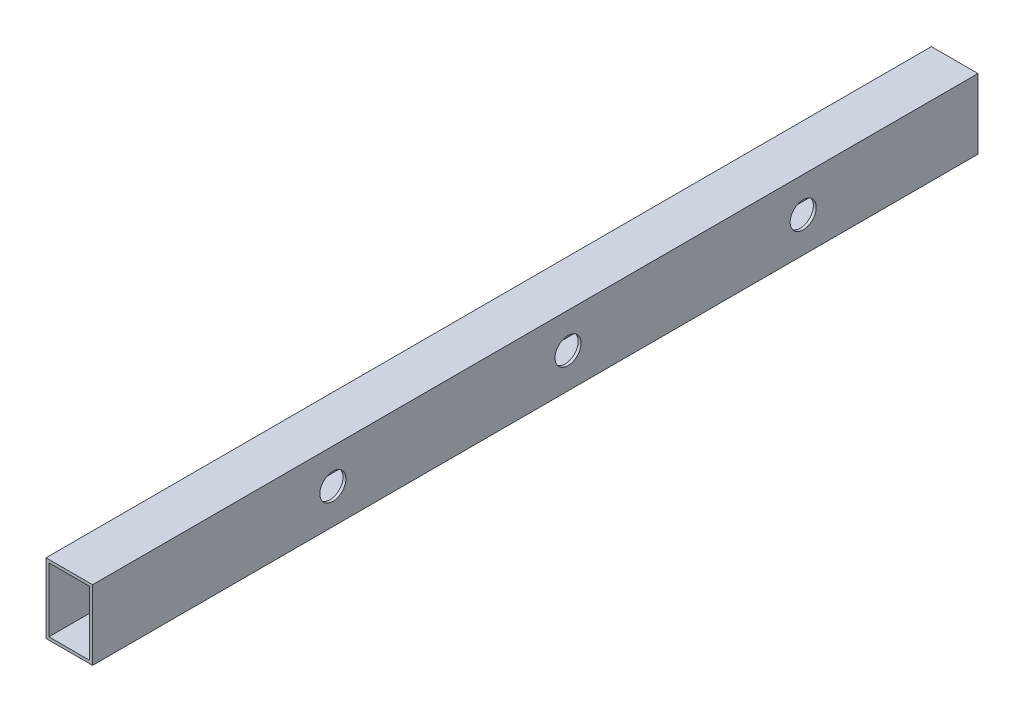
SolidWorks part; units mm, degrees
ref_plane "Front Plane" through (0, 0, 0) normal (0, 0, 1) x (1, 0, 0)
ref_plane "Top Plane" through (0, 0, 0) normal (0, 1, 0) x (1, 0, 0)
ref_plane "Right Plane" through (0, 0, 0) normal (1, 0, 0) x (0, 0, -1)
sketch "Sketch1" plane through (0, 0, 0) normal (0, 0, 1) x (1, 0, 0)
  line L0 (0, 38.1) -> (0, 34.925) construction
  line L1 (-25.4, 38.1) -> (25.4, 38.1)
  line L2 (-25.4, 38.1) -> (-25.4, -38.1)
  line L3 (-25.4, -38.1) -> (25.4, -38.1)
  line L4 (25.4, 38.1) -> (25.4, -38.1)
  line L5 (-25.4, 38.1) -> (25.4, -38.1) construction
  line L6 (-25.4, -38.1) -> (25.4, 38.1) construction
  line L7 (-22.225, 34.925) -> (22.225, 34.925)
  line L8 (-22.225, 34.925) -> (-22.225, -34.925)
  line L9 (-22.225, -34.925) -> (22.225, -34.925)
  line L10 (22.225, 34.925) -> (22.225, -34.925)
  line L11 (22.225, 0) -> (25.4, 0) construction
  line L12 (-22.225, 0) -> (-25.4, 0) construction
  line L13 (0, -34.925) -> (0, -38.1) construction
  point P0 (0, 0)
  dimension "D1" = 76.2
  dimension "D2" = 50.8
  dimension "D3" = 3.175
extrude "Boss-Extrude1" add sketch "Sketch1" along normal blind 965.2
sketch "Sketch2" plane through (0, 38.1, 0) normal (0, 1, 0) x (1, 0, 0)
  line L0 (-26.9875, -190.549) -> (26.9875, -190.549) construction
  line L1 (-25.4, 0) -> (25.4, 0)
  line L2 (-25.4, 0) -> (-25.4, -965.2)
  line L3 (-25.4, -965.2) -> (25.4, -965.2)
  line L4 (25.4, 0) -> (25.4, -965.2)
  line L5 (-26.4963, -703.2466) -> (26.4963, -703.2466) construction
  line L6 (0, -703.2466) -> (0, -190.549) construction
  line L7 (0, 0) -> (0, -190.549) construction
  line L8 (-74.6125, -402.6047) -> (-73.6301, -528.6965) construction
  line L9 (-74.1213, -465.6506) -> (-23.8125, -465.6506) construction
  line L10 (-23.8125, -465.6506) -> (26.9875, -465.6506) construction
  dimension "D1" = 190.549
  dimension "D2" = 512.6976
  dimension "D3" = 126.0917
  dimension "D4" = 50.3088
  dimension "D5" = 50.8
  dimension "D6" = 53.975
  dimension "D7" = 52.9926
  dimension "D8" = 275.1016
ref_plane "Plane1" through (25.4, 0, 0) normal (1, 0, 0) x (0, 0, -1)
sketch "Sketch4" plane through (25.4, 0, 0) normal (1, 0, 0) x (0, 0, -1)
  line L0 (-703.2466, 38.1) -> (-703.2466, 0) construction
  line L1 (-703.2466, 38.1) -> (-190.549, 38.1) construction
  line L2 (-190.549, 38.1) -> (-190.549, 0) construction
  line L3 (0, 38.1) -> (-190.549, 38.1) construction
  line L4 (-190.549, 0) -> (0, 0) construction
  line L5 (0, -38.1) -> (0, 38.1) construction
  line L6 (-190.549, 0) -> (-703.2466, 0) construction
  line L7 (-446.8978, 0) -> (-446.8978, 38.1) construction
  line L8 (-402.6047, 38.1) -> (-528.6965, 38.1) construction
  circle A0 centre (-703.2466, 0) radius 14.224
  circle A1 centre (-190.549, 0) radius 14.224
  circle A2 centre (-446.8978, 0) radius 14.224
  dimension "D1" = 28.448
  dimension "D2" = 512.6976
  dimension "D3" = 190.549
extrude "Cut-Extrude1" cut sketch "Sketch4" against normal up to surface (50.8 mm away) up to face at (-25.4, 0, 482.6)
